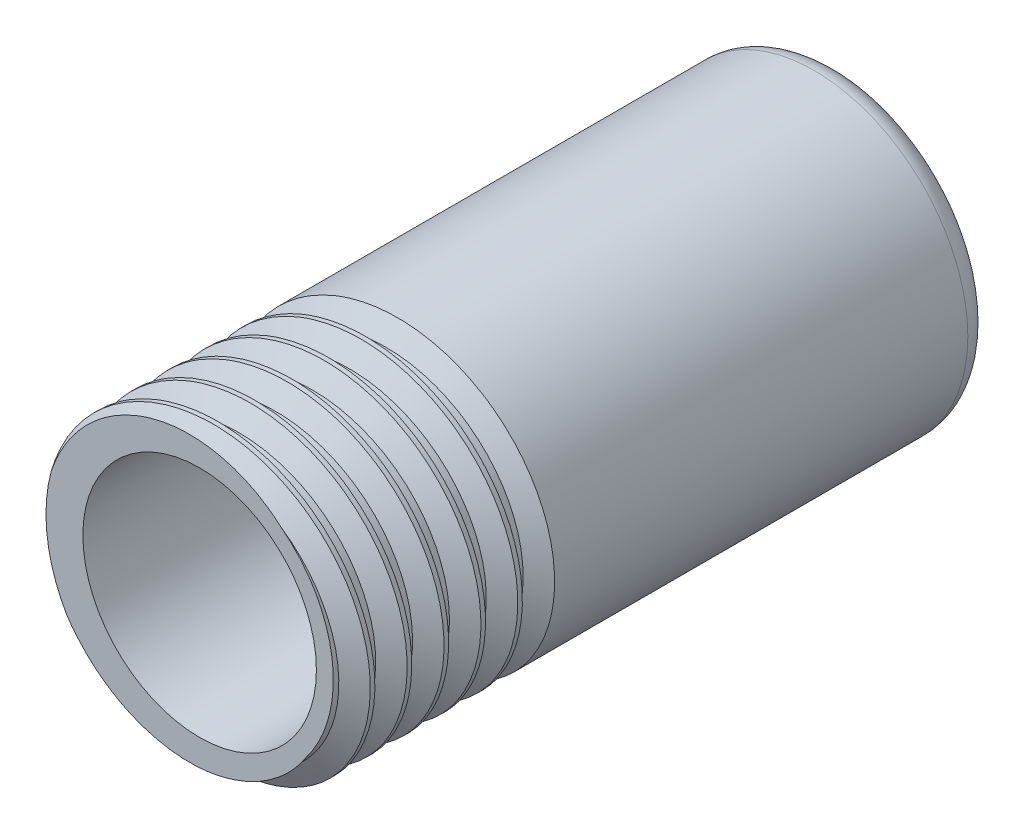
SolidWorks part; units mm, degrees
ref_plane "Alzado" through (0, 0, 0) normal (1, 0, 0) x (0, 1, 0)
ref_plane "Planta" through (0, 0, 0) normal (0, 0, 1) x (0, 1, 0)
ref_plane "Vista lateral" through (0, 0, 0) normal (0, 1, 0) x (-1, 0, 0)
sketch "Croquis2" plane through (0, 0, 0) normal (0, 0, 1) x (0, 1, 0)
  circle A0 centre (0, 0) radius 12.5
  dimension "D1" = 25
extrude "Saliente-Extruir1" add sketch "Croquis2" along normal blind 52
fillet "Redondeo1" radius 2 1 edges at (12.5, 0, 0)
shell "Vaciado1" thickness 3 removed face at (12.5, 0, 52)
thread "Rosca2" pitch 3 method cut trim with start face yes profile "Perfil de rosca2" start angle 0, offset 5.75, length 20.75, pitch 3, diameter 25
ref_plane "Plano2" through (-12.5, 0, 57.75) normal (0, -1, 0) x (-1, 0, 0)
sketch "Perfil de rosca2" plane through (-12.5, 0, 57.75) normal (0, -1, 0) x (-1, 0, 0)
  line L0 (0, 0) -> (0, 3) construction
  line L11 (0, 0) -> (0, 2.625)
  line L12 (0, 2.625) -> (-1.6238, 1.6875)
  line L13 (-1.6238, 1.6875) -> (-1.6238, 0.9375)
  line L15 (-1.6238, 0.9375) -> (0, 0)
  line L17 (-1.6238, 1.3125) -> (0, 1.3125) construction
  point P2 (0, 0)
  dimension "Pitch" = 3
  dimension "Profile_Angle" = 60
  dimension "Profile_Land" = 0.75
  dimension "Profile_Height" = 1.6238
